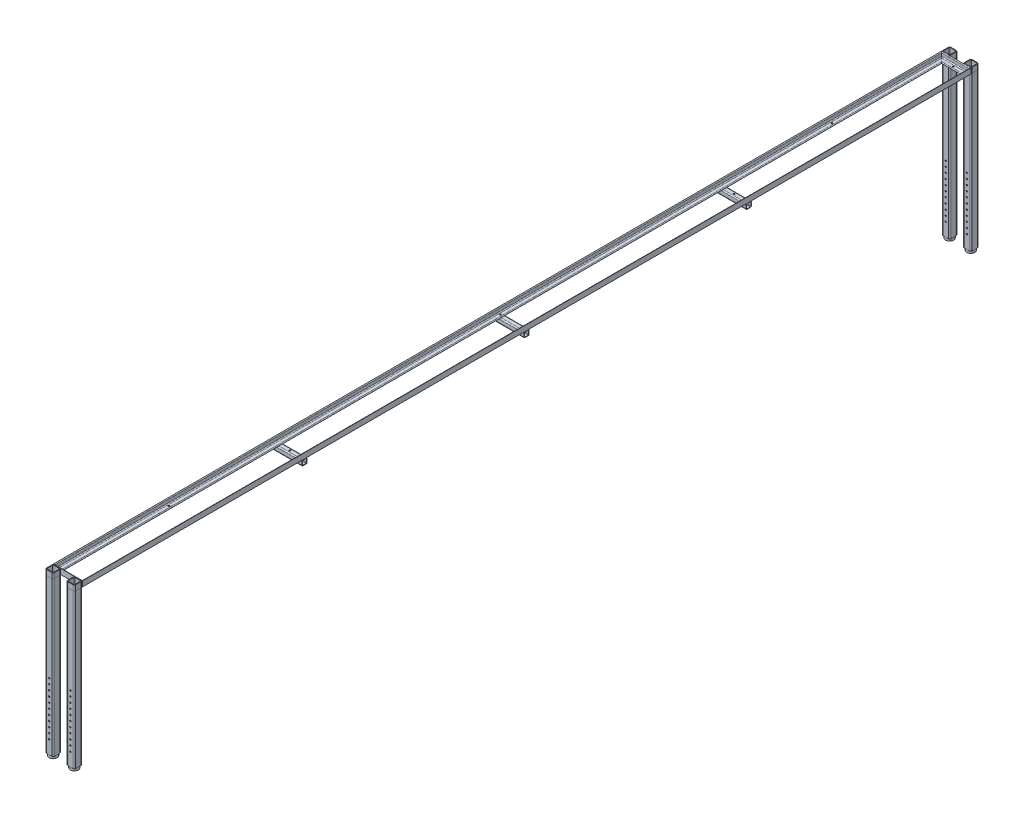
SolidWorks part; units mm, degrees
material "ASTM A36 Steel"
ref_plane "Front Plane" through (0, 0, 0) normal (0, 0, 1) x (1, 0, 0)
ref_plane "Top Plane" through (0, 0, 0) normal (0, 1, 0) x (1, 0, 0)
ref_plane "Right Plane" through (0, 0, 0) normal (1, 0, 0) x (0, 0, -1)
sketch "Sketch2" plane through (0, 0, 0) normal (0, 1, 0) x (1, 0, 0)
  line L0 (375.75, 656.0417) -> (485.75, 656.0417)
  line L1 (375.75, -1856.4583) -> (485.75, -1856.4583)
  line L2 (375.75, -1856.4583) -> (375.75, 1493.5417)
  line L3 (375.75, 1493.5417) -> (485.75, 1493.5417)
  line L4 (485.75, -1856.4583) -> (485.75, 1493.5417)
  line L5 (375.75, -1856.4583) -> (485.75, 1493.5417) construction
  line L6 (375.75, 1493.5417) -> (485.75, -1856.4583) construction
  line L7 (375.75, -1018.9583) -> (485.75, -1018.9583)
  point P0 (430.75, -181.4583)
  dimension "D2" = 110
  dimension "D3" = 837.5
  dimension "D4" = 837.5
other "Angle iron 20 X 20 X 3(2)" corner treatment miter
ref_plane "Plane2" through (485.75, 0, 1856.4583) normal (0, 0, -1) x (-1, 0, 0)
sketch "Sketch1" plane through (485.75, 0, 1856.4583) normal (0, 0, -1) x (-1, 0, 0)
  line L0 (0, 0) -> (0, 20)
  line L1 (0, 10) -> (3, 10) construction
  line L2 (3, 17) -> (3, 6.5)
  line L3 (6.5, 3) -> (17, 3)
  line L4 (10, 3) -> (10, 0) construction
  line L5 (20, 0) -> (0, 0)
  arc A0 (20, 0) -> (17, 3) centre (17, 0) ccw
  arc A1 (0, 20) -> (3, 17) centre (0, 17) cw
  arc A2 (6.5, 3) -> (3, 6.5) centre (6.5, 6.5) cw
  point P10 (10, 0)
  point P14 (0, 10)
  point P15 (3, 10)
  point P16 (10, 3)
  point P17 (3, 20)
  point P18 (20, 3)
  point P21 (0, 0)
  dimension "D2" = 3
  dimension "D3" = 20
  dimension "Radius_1" = 3.5
  dimension "D1" = 3
ref_plane "Plane4" through (0, -10, 0) normal (0, -1, 0) x (-1, 0, 0)
sketch "Sketch12" plane through (0, -10, 0) normal (0, -1, 0) x (-1, 0, 0)
  line L0 (-375.75, 656.0417) -> (-485.75, 656.0417)
other "Square tube 20 X 20 X 2(1)" corner treatment miter
ref_plane "Plane5" through (375.75, -10, -656.0417) normal (1, 0, 0) x (0, 0, 1)
sketch "Sketch13" plane through (375.75, -10, -656.0417) normal (1, 0, 0) x (0, 0, 1)
  line L0 (-6, -8) -> (6, -8)
  line L1 (-8, -6) -> (-8, 6)
  line L2 (6, 8) -> (-6, 8)
  line L3 (8, 6) -> (8, -6)
  line L4 (-6, -10) -> (6, -10)
  line L5 (-10, -6) -> (-10, 6)
  line L6 (6, 10) -> (-6, 10)
  line L7 (10, 6) -> (10, -6)
  arc A0 (10, 6) -> (6, 10) centre (6, 6) ccw
  arc A1 (6, -10) -> (10, -6) centre (6, -6) ccw
  arc A2 (-10, -6) -> (-6, -10) centre (-6, -6) ccw
  arc A3 (-6, 10) -> (-10, 6) centre (-6, 6) ccw
  arc A4 (-6, 8) -> (-8, 6) centre (-6, 6) ccw
  arc A5 (8, 6) -> (6, 8) centre (6, 6) ccw
  arc A6 (6, -8) -> (8, -6) centre (6, -6) ccw
  arc A7 (-8, -6) -> (-6, -8) centre (-6, -6) ccw
  point P0 (-10, 0)
  point P1 (10, 0)
  point P2 (0, 10)
  point P3 (0, -10)
  point P4 (0, 0)
  point P5 (-10, -10)
  point P6 (10, -10)
  point P7 (10, 10)
  point P8 (-10, 10)
  point P33 (0, 0)
  dimension "D1" = 4
  dimension "Thickness" = 2
  dimension "V_leg" = 20
sketch "Sketch14" plane through (0, -10, 0) normal (0, -1, 0) x (-1, 0, 0)
  line L0 (-375.75, -1018.9583) -> (-485.75, -1018.9583)
other "Square tube 20 X 20 X 2(2)" corner treatment miter
ref_plane "Plane6" through (375.75, -10, 1018.9583) normal (1, 0, 0) x (0, 0, 1)
sketch "Sketch15" plane through (375.75, -10, 1018.9583) normal (1, 0, 0) x (0, 0, 1)
  line L0 (-6, -8) -> (6, -8)
  line L1 (-8, -6) -> (-8, 6)
  line L2 (6, 8) -> (-6, 8)
  line L3 (8, 6) -> (8, -6)
  line L4 (-6, -10) -> (6, -10)
  line L5 (-10, -6) -> (-10, 6)
  line L6 (6, 10) -> (-6, 10)
  line L7 (10, 6) -> (10, -6)
  arc A0 (10, 6) -> (6, 10) centre (6, 6) ccw
  arc A1 (6, -10) -> (10, -6) centre (6, -6) ccw
  arc A2 (-10, -6) -> (-6, -10) centre (-6, -6) ccw
  arc A3 (-6, 10) -> (-10, 6) centre (-6, 6) ccw
  arc A4 (-6, 8) -> (-8, 6) centre (-6, 6) ccw
  arc A5 (8, 6) -> (6, 8) centre (6, 6) ccw
  arc A6 (6, -8) -> (8, -6) centre (6, -6) ccw
  arc A7 (-8, -6) -> (-6, -8) centre (-6, -6) ccw
  point P0 (-10, 0)
  point P1 (10, 0)
  point P2 (0, 10)
  point P3 (0, -10)
  point P4 (0, 0)
  point P5 (-10, -10)
  point P6 (10, -10)
  point P7 (10, 10)
  point P8 (-10, 10)
  point P33 (0, 0)
  dimension "D1" = 4
  dimension "Thickness" = 2
  dimension "V_leg" = 20
sketch "Sketch18" plane through (0, 0, 0) normal (0, 1, 0) x (1, 0, 0)
  line L0 (485.75, 662.0417) -> (375.75, 662.0417) construction
  line L1 (485.75, 650.0417) -> (375.75, 650.0417) construction
  circle A0 centre (430.75, 656.0417) radius 2.5
  dimension "D1" = 12
  dimension "D2" = 6
extrude "Cut-Extrude1" cut sketch "Sketch18" against normal through all both and the other way through all
sketch "Sketch19" plane through (0, 0, 0) normal (0, 1, 0) x (1, 0, 0)
  line L0 (485.75, -1012.9583) -> (375.75, -1012.9583) construction
  circle A0 centre (430.75, -1018.9583) radius 2.5
  dimension "D1" = 6
extrude "Cut-Extrude2" cut sketch "Sketch19" against normal through all both and the other way through all
sketch "Sketch20" plane through (0, 3, 0) normal (0, 1, 0) x (1, 0, 0)
  line L0 (479.25, -1849.9583) -> (382.25, -1849.9583) construction
  circle A0 centre (430.75, -1844.7083) radius 2
  dimension "D1" = 5.25
extrude "Cut-Extrude3" cut sketch "Sketch20" against normal through all both and the other way through all
sketch "Sketch21" plane through (0, 3, 0) normal (0, 1, 0) x (1, 0, 0)
  line L0 (382.25, 1487.0417) -> (479.25, 1487.0417) construction
  circle A0 centre (430.75, 1481.7917) radius 2.5
  dimension "D1" = 5.25
extrude "Cut-Extrude4" cut sketch "Sketch21" against normal through all both and the other way through all
sketch "Sketch22" plane through (0, 3, 0) normal (0, 1, 0) x (1, 0, 0)
  circle A0 centre (387.5, 1068.2917) radius 2.5
extrude "Cut-Extrude5" cut sketch "Sketch22" against normal through all both and the other way through all
pattern_linear "LPattern1" count 2 spacing 86.5 along (1, 0, 0) of "Cut-Extrude5"
sketch "Sketch23" plane through (0, 3, 0) normal (0, 1, 0) x (1, 0, 0)
  circle A0 centre (474, -1431.2083) radius 2.5
extrude "Cut-Extrude6" cut sketch "Sketch23" against normal through all both and the other way through all
pattern_linear "LPattern2" count 2 spacing 86.5 along (-1, 0, 0) of "Cut-Extrude6"
sketch "Sketch24" plane through (0, 3, 0) normal (0, 1, 0) x (1, 0, 0)
  line L0 (479.25, -1849.9583) -> (382.25, -1849.9583) construction
  circle A0 centre (387.5, -181.9583) radius 2.5
  dimension "D1" = 1668
extrude "Cut-Extrude7" cut sketch "Sketch24" against normal through all both and the other way through all
pattern_linear "LPattern3" count 2 spacing 86.5 along (1, 0, 0) of "Cut-Extrude7"
ref_plane "Plane7" through (0, 0, 181.4583) normal (0, 0, -1) x (-1, 0, 0)
ref_plane "Plane12" through (0, 0, -1508.5417) normal (0, 0, -1) x (-1, 0, 0)
sketch "Sketch115" plane through (0, 0, -1508.5417) normal (0, 0, -1) x (-1, 0, 0)
  line L0 (-470.75, 0) -> (-470.75, -580)
  line L1 (-375.75, 20) -> (-485.75, 20) construction
  line L2 (-485.75, 0) -> (-485.75, 20) construction
  line L4 (-390.75, 0) -> (-390.75, -580)
  line L5 (-375.75, 20) -> (-375.75, 0) construction
  line L6 (-470.75, 0) -> (-470.75, 20)
  line L7 (-390.75, 0) -> (-390.75, 20)
  dimension "D2" = 15
  dimension "D3" = 600
  dimension "D4" = 15
other "Square tube 30 X 30 X 2.6(2)" corner treatment miter
ref_plane "Plane16" through (470.75, 0, -1508.5417) normal (0, -1, 0) x (-1, 0, 0)
sketch "Sketch118" plane through (470.75, 0, -1508.5417) normal (0, -1, 0) x (-1, 0, 0)
  line L0 (-9.8, -12.4) -> (9.8, -12.4)
  line L1 (-12.4, -9.8) -> (-12.4, 9.8)
  line L2 (9.8, 12.4) -> (-9.8, 12.4)
  line L3 (12.4, 9.8) -> (12.4, -9.8)
  line L4 (-9.8, -15) -> (9.8, -15)
  line L5 (-15, -9.8) -> (-15, 9.8)
  line L6 (9.8, 15) -> (-9.8, 15)
  line L7 (15, 9.8) -> (15, -9.8)
  arc A0 (15, 9.8) -> (9.8, 15) centre (9.8, 9.8) ccw
  arc A1 (9.8, -15) -> (15, -9.8) centre (9.8, -9.8) ccw
  arc A2 (-15, -9.8) -> (-9.8, -15) centre (-9.8, -9.8) ccw
  arc A3 (-9.8, 15) -> (-15, 9.8) centre (-9.8, 9.8) ccw
  arc A4 (-9.8, 12.4) -> (-12.4, 9.8) centre (-9.8, 9.8) ccw
  arc A5 (12.4, 9.8) -> (9.8, 12.4) centre (9.8, 9.8) ccw
  arc A6 (9.8, -12.4) -> (12.4, -9.8) centre (9.8, -9.8) ccw
  arc A7 (-12.4, -9.8) -> (-9.8, -12.4) centre (-9.8, -9.8) ccw
  point P0 (-15, 0)
  point P1 (15, 0)
  point P2 (0, 15)
  point P3 (0, -15)
  point P4 (0, 0)
  point P5 (-15, -15)
  point P6 (15, -15)
  point P7 (15, 15)
  point P8 (-15, 15)
  point P33 (0, 0)
  dimension "D1" = 5.2
  dimension "Thickness" = 2.6
  dimension "V_leg" = 30
ref_plane "Plane17" through (0, 0, 1871.4583) normal (0, 0, 1) x (1, 0, 0)
sketch "Sketch119" plane through (0, 0, 1871.4583) normal (0, 0, 1) x (1, 0, 0)
  line L0 (390.75, 0) -> (390.75, -580)
  line L1 (390.75, 0) -> (390.75, -580) construction
  line L2 (470.75, 0) -> (470.75, -580)
  line L3 (470.75, 0) -> (470.75, -580) construction
  line L4 (390.75, 0) -> (390.75, 20)
  line L5 (470.75, 0) -> (470.75, 20)
  dimension "D1" = 600
  dimension "D2" = 600
other "Square tube 30 X 30 X 2.6(3)" corner treatment miter
ref_plane "Plane18" through (470.75, 0, 1871.4583) normal (0, -1, 0) x (1, 0, 0)
sketch "Sketch120" plane through (470.75, 0, 1871.4583) normal (0, -1, 0) x (1, 0, 0)
  line L0 (-9.8, -12.4) -> (9.8, -12.4)
  line L1 (-12.4, -9.8) -> (-12.4, 9.8)
  line L2 (9.8, 12.4) -> (-9.8, 12.4)
  line L3 (12.4, 9.8) -> (12.4, -9.8)
  line L4 (-9.8, -15) -> (9.8, -15)
  line L5 (-15, -9.8) -> (-15, 9.8)
  line L6 (9.8, 15) -> (-9.8, 15)
  line L7 (15, 9.8) -> (15, -9.8)
  arc A0 (15, 9.8) -> (9.8, 15) centre (9.8, 9.8) ccw
  arc A1 (9.8, -15) -> (15, -9.8) centre (9.8, -9.8) ccw
  arc A2 (-15, -9.8) -> (-9.8, -15) centre (-9.8, -9.8) ccw
  arc A3 (-9.8, 15) -> (-15, 9.8) centre (-9.8, 9.8) ccw
  arc A4 (-9.8, 12.4) -> (-12.4, 9.8) centre (-9.8, 9.8) ccw
  arc A5 (12.4, 9.8) -> (9.8, 12.4) centre (9.8, 9.8) ccw
  arc A6 (9.8, -12.4) -> (12.4, -9.8) centre (9.8, -9.8) ccw
  arc A7 (-12.4, -9.8) -> (-9.8, -12.4) centre (-9.8, -9.8) ccw
  point P0 (-15, 0)
  point P1 (15, 0)
  point P2 (0, 15)
  point P3 (0, -15)
  point P4 (0, 0)
  point P5 (-15, -15)
  point P6 (15, -15)
  point P7 (15, 15)
  point P8 (-15, 15)
  point P33 (0, 0)
  dimension "D1" = 5.2
  dimension "Thickness" = 2.6
  dimension "V_leg" = 30
sketch "Sketch121" plane through (0, 0, 1886.4583) normal (0, 0, 1) x (1, 0, 0)
  line L0 (480.55, -580) -> (460.95, -580) construction
  circle A0 centre (470.75, -530) radius 2.5
  dimension "D1" = 50
extrude "Cut-Extrude9" cut sketch "Sketch121" along normal through all and the other way through all
pattern_linear "LPattern5" count 11 spacing 20 along (0, 1, 0) of "Cut-Extrude9"
sketch "Sketch122" plane through (0, 0, 1886.4583) normal (0, 0, 1) x (1, 0, 0)
  line L4 (400.55, -580) -> (380.95, -580) construction
  circle A0 centre (390.75, -530) radius 2.5
  dimension "D1" = 50
extrude "Cut-Extrude10" cut sketch "Sketch122" against normal through all
pattern_linear "LPattern6" count 11 spacing 20 along (0, 1, 0) of "Cut-Extrude10"
sketch "Sketch123" plane through (0, -580, 0) normal (0, -1, 0) x (1, 0, 0)
  circle A0 centre (470.75, 1871.4583) radius 12.4
  circle A1 centre (470.75, 1871.4583) radius 15
sketch "Sketch124" plane through (0, -580, 0) normal (0, -1, 0) x (1, 0, 0)
  circle A0 centre (390.75, 1871.4583) radius 12.4
  circle A1 centre (390.75, 1871.4583) radius 15
sketch "Sketch125" plane through (0, -580, 0) normal (0, -1, 0) x (1, 0, 0)
  circle A0 centre (390.75, -1508.5417) radius 12.4
  circle A1 centre (390.75, -1508.5417) radius 15
sketch "Sketch126" plane through (0, -580, 0) normal (0, -1, 0) x (1, 0, 0)
  circle A0 centre (470.75, -1508.5417) radius 12.4
  circle A1 centre (470.75, -1508.5417) radius 15
other "Square tube 30 X 30 X 2.6(15)" corner treatment miter
ref_plane "Plane19" through (470.75, 0, -1508.5417) normal (0, 1, 0) x (1, 0, 0)
sketch "Sketch128" plane through (470.75, 0, -1508.5417) normal (0, 1, 0) x (1, 0, 0)
  line L0 (-9.8, -12.4) -> (9.8, -12.4)
  line L1 (-12.4, -9.8) -> (-12.4, 9.8)
  line L2 (9.8, 12.4) -> (-9.8, 12.4)
  line L3 (12.4, 9.8) -> (12.4, -9.8)
  line L4 (-9.8, -15) -> (9.8, -15)
  line L5 (-15, -9.8) -> (-15, 9.8)
  line L6 (9.8, 15) -> (-9.8, 15)
  line L7 (15, 9.8) -> (15, -9.8)
  arc A0 (15, 9.8) -> (9.8, 15) centre (9.8, 9.8) ccw
  arc A1 (9.8, -15) -> (15, -9.8) centre (9.8, -9.8) ccw
  arc A2 (-15, -9.8) -> (-9.8, -15) centre (-9.8, -9.8) ccw
  arc A3 (-9.8, 15) -> (-15, 9.8) centre (-9.8, 9.8) ccw
  arc A4 (-9.8, 12.4) -> (-12.4, 9.8) centre (-9.8, 9.8) ccw
  arc A5 (12.4, 9.8) -> (9.8, 12.4) centre (9.8, 9.8) ccw
  arc A6 (9.8, -12.4) -> (12.4, -9.8) centre (9.8, -9.8) ccw
  arc A7 (-12.4, -9.8) -> (-9.8, -12.4) centre (-9.8, -9.8) ccw
  point P0 (-15, 0)
  point P1 (15, 0)
  point P2 (0, 15)
  point P3 (0, -15)
  point P4 (0, 0)
  point P5 (-15, -15)
  point P6 (15, -15)
  point P7 (15, 15)
  point P8 (-15, 15)
  point P33 (0, 0)
  dimension "D1" = 5.2
  dimension "Thickness" = 2.6
  dimension "V_leg" = 30
other "Square tube 30 X 30 X 2.6(17)" corner treatment miter
ref_plane "Plane20" through (470.75, 0, -1508.5417) normal (0, 1, 0) x (1, 0, 0)
sketch "Sketch129" plane through (470.75, 0, -1508.5417) normal (0, 1, 0) x (1, 0, 0)
  line L0 (-9.8, -12.4) -> (9.8, -12.4)
  line L1 (-12.4, -9.8) -> (-12.4, 9.8)
  line L2 (9.8, 12.4) -> (-9.8, 12.4)
  line L3 (12.4, 9.8) -> (12.4, -9.8)
  line L4 (-9.8, -15) -> (9.8, -15)
  line L5 (-15, -9.8) -> (-15, 9.8)
  line L6 (9.8, 15) -> (-9.8, 15)
  line L7 (15, 9.8) -> (15, -9.8)
  arc A0 (15, 9.8) -> (9.8, 15) centre (9.8, 9.8) ccw
  arc A1 (9.8, -15) -> (15, -9.8) centre (9.8, -9.8) ccw
  arc A2 (-15, -9.8) -> (-9.8, -15) centre (-9.8, -9.8) ccw
  arc A3 (-9.8, 15) -> (-15, 9.8) centre (-9.8, 9.8) ccw
  arc A4 (-9.8, 12.4) -> (-12.4, 9.8) centre (-9.8, 9.8) ccw
  arc A5 (12.4, 9.8) -> (9.8, 12.4) centre (9.8, 9.8) ccw
  arc A6 (9.8, -12.4) -> (12.4, -9.8) centre (9.8, -9.8) ccw
  arc A7 (-12.4, -9.8) -> (-9.8, -12.4) centre (-9.8, -9.8) ccw
  point P0 (-15, 0)
  point P1 (15, 0)
  point P2 (0, 15)
  point P3 (0, -15)
  point P4 (0, 0)
  point P5 (-15, -15)
  point P6 (15, -15)
  point P7 (15, 15)
  point P8 (-15, 15)
  point P33 (0, 0)
  dimension "D1" = 5.2
  dimension "Thickness" = 2.6
  dimension "V_leg" = 30
sketch "Sketch130" plane through (0, -10, 0) normal (0, -1, 0) x (-1, 0, 0)
  line L0 (-485.75, -181.4583) -> (-375.75, -181.4583)
  line L1 (-485.75, 1493.5417) -> (-485.75, -1856.4583) construction
  line L2 (-375.75, -1856.4583) -> (-375.75, 1493.5417) construction
other "Square tube 20 X 20 X 2(7)" corner treatment miter
ref_plane "Plane21" through (485.75, -10, 181.4583) normal (-1, 0, 0) x (0, 0, -1)
sketch "Sketch132" plane through (485.75, -10, 181.4583) normal (-1, 0, 0) x (0, 0, -1)
  line L0 (-6, -8) -> (6, -8)
  line L1 (-8, -6) -> (-8, 6)
  line L2 (6, 8) -> (-6, 8)
  line L3 (8, 6) -> (8, -6)
  line L4 (-6, -10) -> (6, -10)
  line L5 (-10, -6) -> (-10, 6)
  line L6 (6, 10) -> (-6, 10)
  line L7 (10, 6) -> (10, -6)
  arc A0 (10, 6) -> (6, 10) centre (6, 6) ccw
  arc A1 (6, -10) -> (10, -6) centre (6, -6) ccw
  arc A2 (-10, -6) -> (-6, -10) centre (-6, -6) ccw
  arc A3 (-6, 10) -> (-10, 6) centre (-6, 6) ccw
  arc A4 (-6, 8) -> (-8, 6) centre (-6, 6) ccw
  arc A5 (8, 6) -> (6, 8) centre (6, 6) ccw
  arc A6 (6, -8) -> (8, -6) centre (6, -6) ccw
  arc A7 (-8, -6) -> (-6, -8) centre (-6, -6) ccw
  point P0 (-10, 0)
  point P1 (10, 0)
  point P2 (0, 10)
  point P3 (0, -10)
  point P4 (0, 0)
  point P5 (-10, -10)
  point P6 (10, -10)
  point P7 (10, 10)
  point P8 (-10, 10)
  point P33 (0, 0)
  dimension "D1" = 4
  dimension "Thickness" = 2
  dimension "V_leg" = 20
sketch "Sketch134" plane through (0, 3, 0) normal (0, 1, 0) x (1, 0, 0)
  circle A0 centre (387.5, -181.9583) radius 2.5
extrude "Cut-Extrude11" cut sketch "Sketch134" against normal blind 39
sketch "Sketch135" plane through (0, 3, 0) normal (0, 1, 0) x (1, 0, 0)
  circle A0 centre (474, -181.9583) radius 2.5
extrude "Cut-Extrude12" cut sketch "Sketch135" against normal blind 39
sketch "Sketch143" plane through (0, 0, 181.4583) normal (0, 0, -1) x (-1, 0, 0)
  line L0 (-4166.0882, -2710.8093) -> (-3578.7549, -2710.8093) construction
  line L1 (-2258.4652, -2703.2014) -> (-2258.4652, -1285.3354)
  line L2 (-2239.9235, -419.3932) -> (-1127.9489, -419.3932)
  line L3 (-1127.9489, -419.3932) -> (-512.978, -40.5154)
  line L4 (-512.978, -40.5154) -> (-218.5629, -40.5154)
  line L5 (-218.5629, -40.5154) -> (-218.5629, -243.9684)
  line L6 (-218.5629, -243.9684) -> (-1833.7579, -1285.3354)
  line L7 (-1833.7579, -1285.3354) -> (-2258.4652, -1285.3354)
  line L8 (-2239.9235, -419.3932) -> (-3984.2469, -419.3932)
  line L9 (-3984.2469, -419.3932) -> (-4402.5688, -1267.9703)
  line L10 (-4402.5688, -1267.9703) -> (-4402.5688, -2721.9964)
  line L11 (-4402.5688, -2721.9964) -> (-2258.4652, -2721.9964)
  line L12 (-2258.4652, -2721.9964) -> (-2258.4652, -2703.2014)
  line L14 (-2502.4224, 1184.7084) -> (-2318.8357, 886.7219)
  line L20 (-2502.4224, 1184.7084) -> (-670.0936, 41.6729)
  line L22 (-495.8071, 10) -> (-485.75, 10)
  line L23 (-2318.8357, 886.7219) -> (-1425.7276, -562.9154)
  line L24 (-485.75, 20) -> (-485.75, 0) construction
  line L25 (-2502.4224, 1184.7084) -> (-2318.8357, 886.7219)
  line L28 (-495.8071, 10) -> (-1425.7276, -562.9154)
  arc A0 (-495.8071, 10) -> (-670.0936, 41.6729) centre (-543.0673, 245.3008) cw
  dimension "D3" = 1092.2381
  dimension "D1" = 240
  dimension "D2" = 350
  dimension "D4" = 1702.6715
extrude "Boss-Extrude1" add sketch "Sketch126" along normal blind 10 separate body
extrude "Boss-Extrude2" add sketch "Sketch125" along normal blind 10 separate body
extrude "Boss-Extrude3" add sketch "Sketch123" along normal blind 10 separate body
extrude "Boss-Extrude4" add sketch "Sketch124" along normal blind 10 separate body
